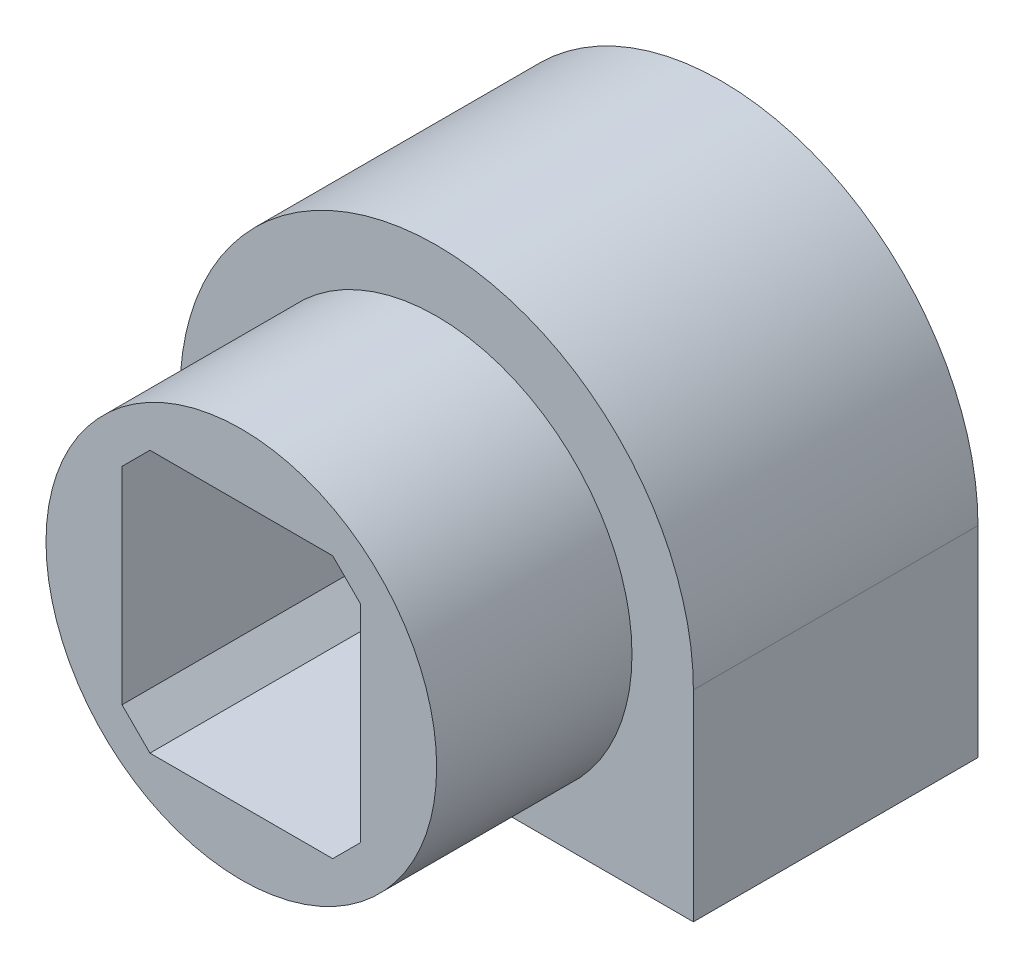
SolidWorks part; units mm, degrees
ref_plane "Alzado" through (0, 0, 0) normal (0, 0, 1) x (1, 0, 0)
ref_plane "Planta" through (0, 0, 0) normal (0, 1, 0) x (1, 0, 0)
ref_plane "Vista lateral" through (0, 0, 0) normal (1, 0, 0) x (0, 0, -1)
sketch "Croquis1" plane through (0, 0, 0) normal (0, 0, 1) x (1, 0, 0)
  line L1 (0, 0) -> (92, 0)
  line L2 (0, 0) -> (0, 36)
  line L4 (92, 0) -> (92, 36)
  arc A0 (92, 36) -> (0, 36) centre (46, 36) ccw
  dimension "D3" = 46
  dimension "D4" = 36
  dimension "D1" = 92
  dimension "D2" = 36
extrude "Saliente-Extruir1" add sketch "Croquis1" against normal blind 51
sketch "Croquis2" plane through (0, 0, 0) normal (0, 0, 1) x (1, 0, 0)
  circle A0 centre (46, 36) radius 35
  dimension "D1" = 70
extrude "Saliente-Extruir3" add sketch "Croquis2" along normal blind 35 contours A0
sketch "Croquis4" plane through (0, 0, 35) normal (0, 0, 1) x (1, 0, 0)
  line L0 (24.625, 54.5) -> (29.625, 59.5)
  line L1 (29.625, 59.5) -> (62.375, 59.5)
  line L2 (24.625, 54.5) -> (24.625, 17.5)
  line L3 (29.625, 12.5) -> (62.375, 12.5)
  line L4 (67.375, 54.5) -> (67.375, 17.5)
  line L5 (62.375, 59.5) -> (67.375, 54.5)
  line L6 (62.375, 12.5) -> (67.375, 17.5)
  line L7 (24.625, 17.5) -> (29.625, 12.5)
  circle A0 centre (46, 36) radius 35 construction
  point P0 (24.625, 59.5)
  point P1 (67.375, 12.5)
  point P2 (24.625, 12.5)
  point P3 (67.375, 59.5)
  dimension "D1" = 5
  dimension "D2" = 5
  dimension "D3" = 5
  dimension "D4" = 5
  dimension "D5" = 5
  dimension "D6" = 5
  dimension "D7" = 5
  dimension "D8" = 5
  dimension "D9" = 42.75
  dimension "D10" = 21.375
  dimension "D11" = 23.5
  dimension "D12" = 47
extrude "Cortar-Extruir1" cut sketch "Croquis4" against normal blind 53 contours L0 L1 L5 L4 L6 L3 L7 L2
sketch "Croquis5" plane through (0, 0, -18) normal (0, 0, 1) x (1, 0, 0)
  line L1 (29.625, 12.5) -> (62.375, 12.5) construction
  line L2 (34, 12.5) -> (58, 12.5)
  line L3 (34, 12.5) -> (34, 21.9199)
  line L4 (34, 21.9199) -> (58, 21.9199)
  line L5 (58, 12.5) -> (58, 21.9199)
  circle A0 centre (46, 36) radius 18.5
  circle A1 centre (46, 36) radius 35 construction
  line M6 (29.625, 12.5) -> (62.375, 12.5)
  dimension "D1" = 37
  dimension "D2" = 24
extrude "Cortar-Extruir2" cut sketch "Croquis5" against normal blind 30 contours L4 A0 | L4 A0 | A0 L3 L5 M6 region at (46, 15.8274, -18) region at (46, 37.149, -18) region at (46, 20.1325, -18)
sketch "Croquis6" plane through (0, 0, -48) normal (0, 0, 1) x (1, 0, 0)
  line L0 (46, 36) -> (46, 50)
  line L1 (46, 36) -> (54.8388, 44.8388)
  line L2 (46, 36) -> (36.1005, 45.8995)
  circle A0 centre (46, 36) radius 11.5
  arc A1 (54.7835, 46.9018) -> (56.9018, 44.7835) centre (46, 36) ccw
  circle A2 centre (55.8995, 45.8995) radius 1.5
  circle A3 centre (36.1005, 45.8995) radius 1.5
  circle A4 centre (36.1005, 26.1005) radius 1.5
  circle A5 centre (55.8995, 26.1005) radius 1.5
  point P18 (46, 36)
  dimension "D1" = 23
  dimension "D2" = 28
  dimension "D3" = 3
  dimension "D4" = 9.8995
  dimension "D8" = 45
  dimension "D5" = 45
  dimension "D7" = 19.799
  dimension "D6" = 4
extrude "Cortar-Extruir3" cut sketch "Croquis6" against normal blind 27 contours A1 A4 | A1 A4 | A1 A5 | A1 A5 | A2 | L2 A0 L1 | L1 A0 L0 | L0 A0 L2 | A3 region at (43.1409, 42.9024, -48) region at (48.8591, 42.9024, -48) region at (46, 33.6992, -48) region at (55.8995, 45.8995, -48) region at (56.3393, 25.6607, -48) region at (55.4393, 26.5607, -48) region at (36.5607, 26.5607, -48) region at (35.6607, 25.6607, -48)
sketch "Croquis7" plane through (0, 0, -51) normal (0, 0, -1) x (-1, 0, 0)
  line L1 (-61.5, 20.5) -> (-30.5, 20.5)
  line L2 (-61.5, 20.5) -> (-61.5, 51.5)
  line L3 (-61.5, 51.5) -> (-30.5, 51.5)
  line L4 (-30.5, 20.5) -> (-30.5, 51.5)
  circle A0 centre (-46, 36) radius 11.5 construction
  circle A1 centre (-61.5, 51.5) radius 3
  circle A2 centre (-30.5, 51.5) radius 3
  circle A3 centre (-30.5, 20.5) radius 3
  circle A4 centre (-61.5, 20.5) radius 3
  dimension "D5" = 6
  dimension "D6" = 6
  dimension "D7" = 6
  dimension "D8" = 6
  dimension "D1" = 31
  dimension "D2" = 31
  dimension "D3" = 15.5
  dimension "D4" = 15.5
extrude "Cortar-Extruir4" cut sketch "Croquis7" against normal blind 29 contours L3 A1 L2 | L2 A1 L3 | L2 A4 L1 | L1 A4 L2 | L4 A3 L1 | L1 A3 L4 | L3 A2 L4 | L4 A2 L3 region at (60.2268, 21.7732, -51) region at (61.9244, 20.0756, -51) region at (31.7732, 21.7732, -51) region at (30.0756, 20.0756, -51) region at (61.9244, 51.9244, -51) region at (60.2268, 50.2268, -51) region at (31.7732, 50.2268, -51) region at (30.0756, 51.9244, -51)
sketch "Croquis8" plane through (0, 0, -22) normal (0, 0, -1) x (-1, 0, 0)
  circle A0 centre (-61.5, 51.5) radius 1.5
  circle A1 centre (-30.5, 51.5) radius 1.5
  circle A2 centre (-30.5, 20.5) radius 1.5
  circle A3 centre (-61.5, 20.5) radius 1.5
  dimension "D1" = 3
  dimension "D2" = 3
  dimension "D3" = 3
  dimension "D4" = 3
extrude "Cortar-Extruir5" cut sketch "Croquis8" against normal through all
sketch "Croquis9" plane through (0, 0, -51) normal (0, 0, -1) x (-1, 0, 0)
  line L0 (-46, 69.0406) -> (-46, 0)
  line L1 (0, 0) -> (-92, 0) construction
  circle A5 centre (-46, 52.25) radius 1
  circle A6 centre (-46, 59) radius 1
  circle A7 centre (-46, 19.75) radius 1
  circle A8 centre (-46, 13) radius 1
  circle A9 centre (-46, 36) radius 11.5 construction
  dimension "D1" = 2
  dimension "D2" = 2
  dimension "D3" = 2
  dimension "D4" = 2
  dimension "D5" = 16.25
  dimension "D6" = 16.25
  dimension "D7" = 23
  dimension "D8" = 23
extrude "Cortar-Extruir6" cut sketch "Croquis9" against normal blind 4 contours L0 A6 | L0 A6 | L0 A5 | L0 A5 | L0 A7 | L0 A7 | L0 A8 | L0 A8 region at (45.5756, 59, -51) region at (45.5756, 13, -51) region at (46.4244, 13, -51) region at (45.5756, 19.75, -51) region at (46.4244, 19.75, -51) region at (45.5756, 52.25, -51) region at (46.4244, 52.25, -51) region at (46.4244, 59, -51)
sketch "Croquis10" plane through (0, 0, 0) normal (0, -1, 0) x (1, 0, 0)
  line L0 (46, -17) -> (46, -5) construction
  line L2 (0, 0) -> (92, 0) construction
  line L4 (0, -51) -> (0, 0) construction
  circle A4 centre (46, -17) radius 12
  circle A5 centre (46, -5) radius 1.5
  circle A6 centre (58, -17) radius 1.5
  circle A7 centre (46, -29) radius 1.5
  circle A8 centre (34, -17) radius 1.5
  dimension "D1" = 24
  dimension "D2" = 17
  dimension "D3" = 46
  dimension "D4" = 3
  dimension "D5" = 4
  dimension "D6" = 12
extrude "Cortar-Extruir7" cut sketch "Croquis10" against normal up to surface (12.5 mm away) contours A5 | A8 | A6 | A7 up to face at (46, 12.5, -24)
sketch "Croquis11" plane through (0, 0, 0) normal (0, -1, 0) x (1, 0, 0)
  line L0 (0, -51) -> (92, -51) construction
  line L1 (34, -37) -> (58, -37)
  line L2 (34, -37) -> (34, -45)
  line L3 (34, -45) -> (58, -45)
  line L4 (58, -37) -> (58, -45)
  line L5 (0, -51) -> (0, 0) construction
  line L6 (92, -51) -> (92, 0) construction
  dimension "D1" = 6
  dimension "D2" = 8
  dimension "D3" = 34
  dimension "D4" = 34
extrude "Cortar-Extruir8" cut sketch "Croquis11" against normal blind 18
sketch "Croquis12" plane through (0, 12.5, 0) normal (0, 1, 0) x (1, 0, 0)
  circle A0 centre (34, 17) radius 3.5
  circle A1 centre (34, 17) radius 1.5 construction
  circle A2 centre (58, 17) radius 3.5
  dimension "D1" = 7
  dimension "D2" = 7
extrude "Cortar-Extruir9" cut sketch "Croquis12" along normal blind 5
sketch "Croquis13" plane through (0, 0, 0) normal (0, -1, 0) x (1, 0, 0)
  circle A0 centre (46, -17.0001) radius 16.5
  circle A1 centre (46, -5) radius 1.5 construction
  circle A3 centre (34, -17) radius 1.5 construction
  dimension "D1" = 33
  dimension "D2" = 12.0001
  dimension "D3" = 12
extrude "Cortar-Extruir10" cut sketch "Croquis13" against normal blind 3
ref_axis "Eje1" through (46, 36, -51) along (0, 0, 1)
ref_axis "Eje2" through (46, 42.8122, -17.0001) along (0, -1, 0)
ref_point "Point1"
